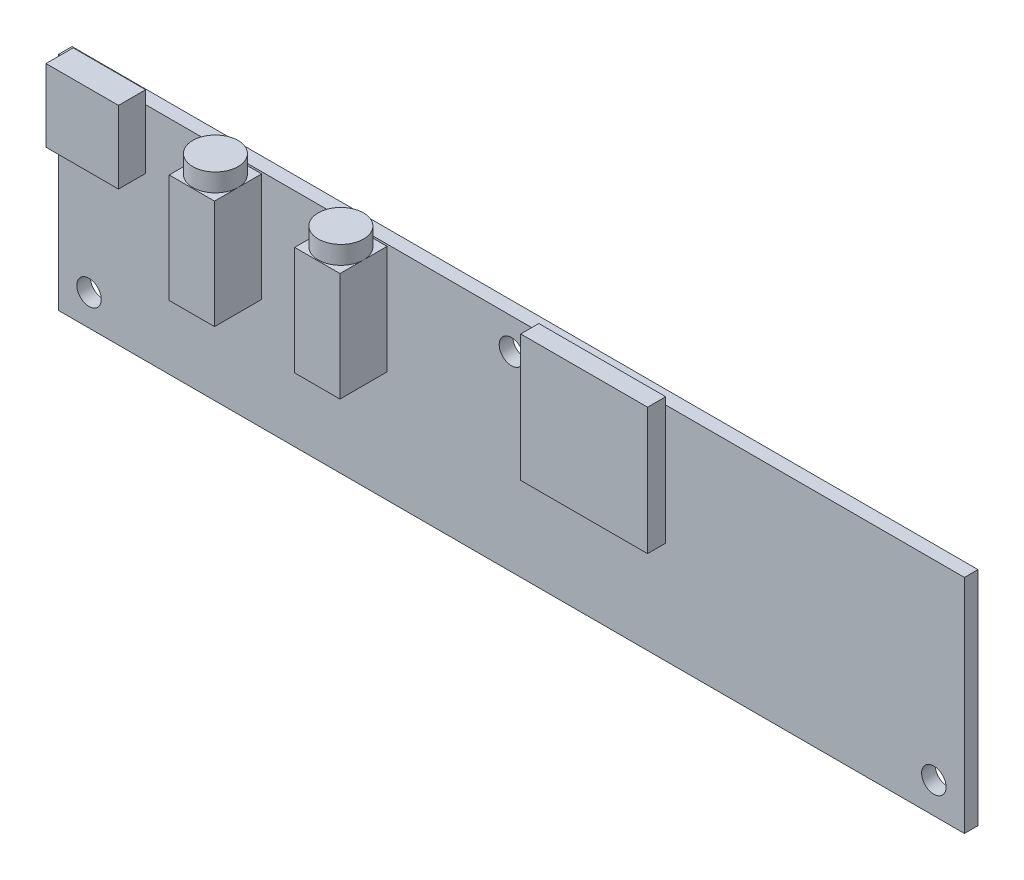
SolidWorks part; units mm, degrees
ref_plane "Спереди" through (0, 0, 0) normal (0, 0, 1) x (1, 0, 0)
ref_plane "Сверху" through (0, 0, 0) normal (0, 1, 0) x (1, 0, 0)
ref_plane "Справа" through (0, 0, 0) normal (1, 0, 0) x (0, 0, -1)
sketch "Эскиз1" plane through (0, 0, 0) normal (0, 0, 1) x (1, 0, 0)
  line L1 (-50, -12.24) -> (50, -12.24)
  line L2 (-50, -12.24) -> (-50, 12.24)
  line L3 (-50, 12.24) -> (50, 12.24)
  line L4 (50, -12.24) -> (50, 12.24)
  line L5 (-50, -12.24) -> (50, 12.24) construction
  line L6 (-50, 12.24) -> (50, -12.24) construction
  circle A0 centre (-46.625, -8.825) radius 1.35
  circle A1 centre (46.625, -8.825) radius 1.35
  circle A2 centre (0, 8.825) radius 1.35
  point P0 (0, 0)
  dimension "D3" = 2.7
  dimension "D1" = 100
  dimension "D2" = 24.48
  dimension "D4" = 93.25
  dimension "D5" = 46.625
  dimension "D6" = 17.65
  dimension "D7" = 3.415
extrude "Бобышка-Вытянуть1" add sketch "Эскиз1" along normal blind 1.5
sketch "Эскиз2" plane through (0, 0, 1.5) normal (0, 0, 1) x (1, 0, 0)
  line L1 (-48.375, 13.675) -> (-40.375, 13.675)
  line L2 (-48.375, 13.675) -> (-48.375, 5.675)
  line L3 (-48.375, 5.675) -> (-40.375, 5.675)
  line L4 (-40.375, 13.675) -> (-40.375, 5.675)
  line L5 (-48.375, 13.675) -> (-40.375, 5.675) construction
  line L6 (-48.375, 5.675) -> (-40.375, 13.675) construction
  line L7 (-32.575, 12.025) -> (-27.575, 12.025)
  line L8 (-32.575, 12.025) -> (-32.575, 0.025)
  line L9 (-32.575, 0.025) -> (-27.575, 0.025)
  line L10 (-27.575, 12.025) -> (-27.575, 0.025)
  line L11 (-32.575, 12.025) -> (-27.575, 0.025) construction
  line L12 (-32.575, 0.025) -> (-27.575, 12.025) construction
  line L13 (-18.725, 12.025) -> (-13.725, 12.025)
  line L14 (-18.725, 12.025) -> (-18.725, 0.025)
  line L15 (-18.725, 0.025) -> (-13.725, 0.025)
  line L16 (-13.725, 12.025) -> (-13.725, 0.025)
  line L17 (-18.725, 12.025) -> (-13.725, 0.025) construction
  line L18 (-18.725, 0.025) -> (-13.725, 12.025) construction
  line L19 (3.025, 13.025) -> (17.025, 13.025)
  line L20 (3.025, 13.025) -> (3.025, -0.975)
  line L21 (3.025, -0.975) -> (17.025, -0.975)
  line L22 (17.025, 13.025) -> (17.025, -0.975)
  line L23 (3.025, 13.025) -> (17.025, -0.975) construction
  line L24 (3.025, -0.975) -> (17.025, 13.025) construction
  point P0 (-44.375, 9.675)
  point P5 (-30.075, 6.025)
  point P7 (-46.625, -8.825)
  point P12 (-16.225, 6.025)
  point P19 (10.025, 6.025)
  line M3 (50, 12.24) -> (-50, 12.24)
  dimension "D2" = 2.25
  dimension "D1" = 8
  dimension "D3" = 18.5
  dimension "D4" = 8
  dimension "D5" = 14.3
  dimension "D6" = 13.85
  dimension "D7" = 3.65
  dimension "D8" = 12
  dimension "D9" = 5
  dimension "D10" = 26.25
  dimension "D11" = 14
  dimension "D12" = 14
extrude "Бобышка-Вытянуть2" add sketch "Эскиз2" along normal blind 5.2 contours L10 L7 L8 L9 | L16 L13 L14 L15 region at (-30.075, 6.025, 1.5) region at (-16.225, 6.025, 1.5)
extrude "Бобышка-Вытянуть3" add sketch "Эскиз2<3>" along normal blind 3 contours L4 L2 L3 M3 | L2 L1 L4 L3 region at (-44.375, 8.9575, 1.5)
sketch "Эскиз2<3>" plane through (0, 0, 1.5) normal (0, 0, 1) x (1, 0, 0) same geometry as "Эскиз2"
sketch "Эскиз3" plane through (0, 12.025, 0) normal (0, 1, 0) x (1, 0, 0)
  line L0 (-13.725, -6.7) -> (-13.725, -1.5) construction
  line L1 (-18.725, -6.7) -> (-13.725, -6.7) construction
  line L2 (-32.575, -6.7) -> (-27.575, -6.7) construction
  line L3 (-27.575, -6.7) -> (-27.575, -1.5) construction
  circle A0 centre (-16.225, -4.1) radius 2.5
  circle A1 centre (-30.075, -4.1) radius 2.5
  point P7 (-13.725, -4.1)
  point P10 (-16.225, -6.7)
  point P13 (-30.075, -6.7)
  point P16 (-27.575, -4.1)
  dimension "D1" = 5
extrude "Бобышка-Вытянуть4" add sketch "Эскиз3" along normal blind 2
extrude "Бобышка-Вытянуть5" add sketch "Эскиз2<4>" along normal blind 2
sketch "Эскиз2<4>" plane through (0, 0, 1.5) normal (0, 0, 1) x (1, 0, 0) same geometry as "Эскиз2"
